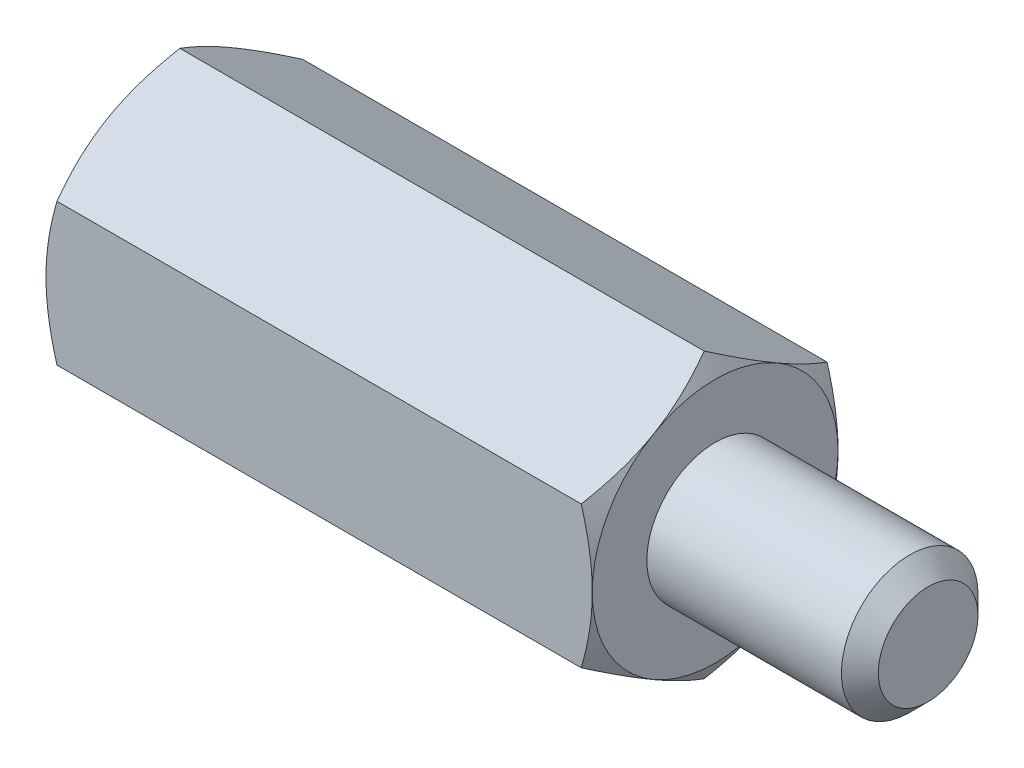
SolidWorks part; units mm, degrees
ref_plane "Front Plane" through (0, 0, 0) normal (0, 0, 1) x (1, 0, 0)
ref_plane "Top Plane" through (0, 0, 0) normal (0, 1, 0) x (1, 0, 0)
ref_plane "Right Plane" through (0, 0, 0) normal (1, 0, 0) x (0, 0, -1)
sketch "Sketch1" plane through (0, 0, 0) normal (0, 0, 1) x (1, 0, 0)
  line L0 (-6.95, 0) -> (6.95, 0) construction
  line L1 (6.95, 1.25) -> (6.95, -1.25) construction
  line L2 (-6.95, 2.25) -> (-6.95, -2.25) construction
  line L3 (-2.15, 1.25) -> (-2.15, -1.25) construction
  line L4 (-2.15, -1.25) -> (-6.95, -1.25) construction
  line L5 (-2.15, 1.25) -> (-6.95, 1.25) construction
  line L6 (-6.95, 2.25) -> (3.05, 2.25) construction
  line L7 (-6.95, -2.25) -> (3.05, -2.25) construction
  point P2 (3.05, 0)
  point P8 (-2.15, 0)
  point P13 (4.925, -1.25)
  dimension "Hex" = 4.5
  dimension "Male Thread" = 2.5
  dimension "A" = 10
  dimension "B" = 3.9
  dimension "C" = 4.8
  dimension "Female Thread" = 2.5
  dimension "D1" = 2.025
ref_plane "Plane1" through (6.95, 0, 0) normal (1, 0, 0) x (0, 0, -1)
sketch "Sketch2" plane through (6.95, 0, 0) normal (1, 0, 0) x (0, 0, -1)
  circle A0 centre (0, 0) radius 1.25
extrude "Extrude1" add sketch "Sketch2" against normal up to vertex (3.9 mm away) up to point (3.05, 0, 0)
sketch "Sketch3" plane through (6.95, 0, 0) normal (1, 0, 0) x (0, 0, -1)
  circle A1 centre (0, 0) radius 1.25
  circle A2 centre (0, 0) radius 1.25
  dimension "D1" = 0
curve "Helix/Spiral1" pitch 0.45 height 4.35 turns 9.6667 parameters "Male Pitch"=0.45
chamfer "Chamfer1" distance 0.3375 angle 45 1 edges at (6.95, 0, -1.25)
sketch "Sketch4" plane through (0, 0, 0) normal (0, 0, 1) x (1, 0, 0)
  line L0 (6.95, 1.25) -> (7.3438, 1.25)
  line L1 (7.3438, 1.25) -> (7.175, 0.9577)
  line L2 (7.175, 0.9577) -> (7.1188, 0.9577)
  line L3 (7.1188, 0.9577) -> (6.95, 1.25)
  line L4 (7.1469, 0.9577) -> (7.1469, 1.25) construction
  line L5 (7.0344, 1.1039) -> (7.2594, 1.1039) construction
  dimension "D1" = 0.0563
  dimension "D2" = 0.225
  dimension "D3" = 60
sweep "Cut-Sweep1" [suppressed] cut profiles "Sketch4" path "Helix/Spiral1"
sketch "Sketch16" [suppressed] plane through (0, 0, 0) normal (0, 0, 1) x (1, 0, 0)
  line L0 (3.05, 0.9552) -> (3.8375, 0.9552)
  line L1 (3.8375, 0.9552) -> (4.1323, 1.25)
  line L2 (4.1323, 1.25) -> (3.05, 1.25)
  line L3 (3.05, 1.25) -> (3.05, 0.9552)
  line L4 (6.95, 1.25) -> (7.3438, 1.25) construction
  line L5 (0, 0) -> (6.95, 0) construction
  line L6 (6.95, -0.9125) -> (6.95, 0.9125) construction
  dimension "D1" = 0.7875
  dimension "D2" = 45
  dimension "D3" = 0.0025
revolve "Cut-Revolve1" [suppressed] cut sketch "Sketch16" angle 360 about L5
ref_plane "Plane2" through (3.05, 0, 0) normal (1, 0, 0) x (0, 0, -1)
sketch "Sketch7" plane through (3.05, 0, 0) normal (1, 0, 0) x (0, 0, -1)
  line L1 (0, 2.5981) -> (-2.25, 1.299)
  line L2 (-2.25, 1.299) -> (-2.25, -1.299)
  line L3 (-2.25, -1.299) -> (0, -2.5981)
  line L4 (0, -2.5981) -> (2.25, -1.299)
  line L5 (2.25, -1.299) -> (2.25, 1.299)
  line L6 (2.25, 1.299) -> (0, 2.5981)
  circle A0 centre (0, 0) radius 2.25 construction
extrude "Extrude4" add sketch "Sketch7" against normal up to vertex (10 mm away) up to point (-6.95, 0, 0)
sketch "Sketch17" plane through (0, 0, 0) normal (0, 0, 1) x (1, 0, 0)
  line L0 (-6.95, -2.5981) -> (3.05, -2.5981) construction
  line L1 (-6.95, 2.5981) -> (3.05, 2.5981) construction
  line L2 (-6.95, -2.5981) -> (3.05, -2.5981)
  line L3 (-6.95, 2.5981) -> (3.05, 2.5981)
sketch "Sketch8" plane through (-6.95, 0, 0) normal (-1, 0, 0) x (0, 0, 1)
  circle A0 centre (0, 0) radius 2.25 construction
  circle A1 centre (0, 0) radius 2.25
extrude "Extrude5" cut sketch "Sketch8" against normal through all draft 60 flip side to cut
sketch "Sketch9" plane through (3.05, 0, 0) normal (1, 0, 0) x (0, 0, -1)
  circle A0 centre (0, 0) radius 2.25 construction
  circle A1 centre (0, 0) radius 2.25
extrude "Extrude6" cut sketch "Sketch9" against normal through all draft 60 flip side to cut
sketch "Sketch10" plane through (-6.95, 0, 0) normal (-1, 0, 0) x (0, 0, 1)
  line L0 (0, 0) -> (-0.8839, 0.8839) construction
  line L1 (0, 0) -> (-1.25, 0) construction
  circle A0 centre (0, 0) radius 1.25
  dimension "D1" = 45
extrude "Extrude7" cut sketch "Sketch10" against normal up to vertex (4.8 mm away) up to point (-2.15, 0, 0)
sketch "Sketch11" plane through (-6.95, 0, 0) normal (-1, 0, 0) x (0, 0, 1)
  circle A0 centre (0, 0) radius 1.25 construction
  circle A1 centre (0, 0) radius 1.25
curve "Helix/Spiral2" pitch 0.45 height 4.8 turns 10.6667 parameters "Female Pitch"=0.45
sketch "Sketch12" plane through (0, 0, 0) normal (0, 0, 1) x (1, 0, 0)
  line L0 (-7.3437, 1.25) -> (-7.175, 0.9577)
  line L1 (-7.175, 0.9577) -> (-7.1188, 0.9577)
  line L2 (-7.1188, 0.9577) -> (-6.95, 1.25)
  line L3 (-7.3437, 1.25) -> (-6.95, 1.25)
  line L4 (-7.1469, 0.9577) -> (-7.1469, 1.25) construction
  line L5 (-6.95, 2.25) -> (-6.95, -2.25) construction
  line L6 (-7.2594, 1.1039) -> (-7.0344, 1.1039) construction
  dimension "D1" = 60
  dimension "D2" = 0.0563
  dimension "D3" = 0.225
sweep "Sweep3" [suppressed] add profiles "Sketch12" path "Helix/Spiral2"
sketch "Sketch13" plane through (-6.95, 0, 0) normal (-1, 0, 0) x (0, 0, 1)
  circle A2 centre (0, 0) radius 1.3008
  circle A3 centre (0, 0) radius 1.3008
  dimension "D1" = 0.0508
extrude "Extrude8" cut sketch "Sketch13" along normal through all and the other way through all draft 45
equation "\"D3@Helix/Spiral1\" = \"B@Sketch1\"+\"Male Pitch@Helix/Spiral1\"*1"
equation "\"D1@Chamfer1\" = \"Male Pitch@Helix/Spiral1\"*.750"
equation "\"D1@Sketch4\" = \"Male Pitch@Helix/Spiral1\"*.125"
equation "\"D2@Sketch4\" = \"Male Pitch@Helix/Spiral1\"*.5"
equation "\"D2@Sketch12\" = \"Male Pitch@Helix/Spiral1\"*.125"
equation "\"D3@Sketch12\" = \"Male Pitch@Helix/Spiral1\"*.5"
equation "\"D3@Helix/Spiral2\" = \"C@Sketch1\""
equation "\"Female Thread@Sketch1\" = \"Male Thread@Sketch1\""
equation "\"Female Pitch@Helix/Spiral2\" = \"Male Pitch@Helix/Spiral1\""
equation "\"D1@Sketch16\" = \"Male Pitch@Helix/Spiral1\"*1.75"
equation "\"D1@Sketch1\" = \"Male Pitch@Helix/Spiral1\"*4.5"
